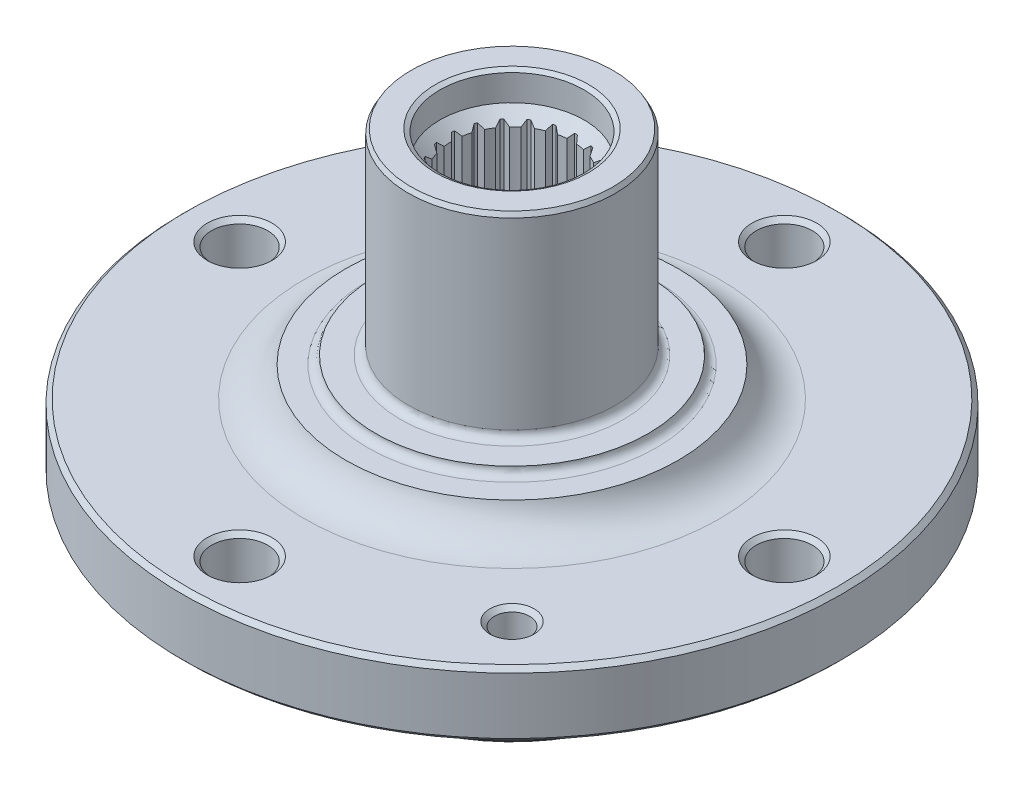
SolidWorks part; units mm, degrees
ref_plane "Front Plane" through (0, 0, 0) normal (0, 0, 1) x (1, 0, 0)
ref_plane "Top Plane" through (0, 0, 0) normal (0, 1, 0) x (1, 0, 0)
ref_plane "Right Plane" through (0, 0, 0) normal (1, 0, 0) x (0, 0, -1)
sketch "Sketch1" plane through (0, 0, 0) normal (0, 0, 1) x (1, 0, 0)
  line L0 (0, 72.238) -> (0, -80.5296) construction
  line L1 (13.25, 37.5) -> (13.25, 32.5)
  line L2 (13.25, 32.5) -> (11, 32.5)
  line L3 (11, 32.5) -> (11, -18.5)
  line L4 (11, -18.5) -> (25.5, -18.5)
  line L5 (25.5, -18.5) -> (25.5, -34.5)
  line L6 (25.5, -34.5) -> (28, -34.5)
  line L7 (28, -34.5) -> (28, -39.5)
  line L8 (30.25, -17.5) -> (30.25, -26)
  line L9 (30.25, -26) -> (30, -26)
  line L10 (30.25, -17.5) -> (60.5, -17.5)
  line L11 (60.5, -17.5) -> (60.5, -5.5)
  line L12 (60.5, -5.5) -> (30.5, -5.5)
  line L13 (30.5, -5.5) -> (30.5, 0)
  line L14 (30.5, 0) -> (25, 0)
  line L15 (25, 0) -> (25, 1.5)
  line L16 (25, 1.5) -> (19, 1.5)
  line L17 (19, 1.5) -> (19, 37.5)
  line L18 (13.25, 37.5) -> (19, 37.5)
  line L19 (30, -26) -> (30, -35)
  line L20 (30, -35) -> (29.5, -35)
  line L21 (29.5, -35) -> (29.5, -39.5)
  line L22 (29.5, -39.5) -> (28, -39.5)
  dimension "D1" = 11
  dimension "D2" = 5
  dimension "D3" = 19
  dimension "D4" = 25
  dimension "D5" = 30.5
  dimension "D6" = 60.5
  dimension "D7" = 25.5
  dimension "D8" = 28
  dimension "D9" = 30.25
  dimension "D10" = 30
  dimension "D11" = 29.5
  dimension "D12" = 5
  dimension "D13" = 21
  dimension "D14" = 12
  dimension "D15" = 13.25
  dimension "D16" = 36
  dimension "D17" = 1.5
  dimension "D18" = 5.5
  dimension "D19" = 5.5
  dimension "D20" = 8.5
  dimension "D21" = 17.5
  dimension "D22" = 22
revolve "Revolve1" add sketch "Sketch1" angle 360 about L0
sketch "Sketch2" plane through (0, -17.5, 0) normal (0, -1, 0) x (1, 0, 0)
  line L0 (0, 0) -> (-50, 0) construction
  circle A0 centre (0, 0) radius 50 construction
  circle A1 centre (-50, 0) radius 5.15
  circle A2 centre (35.3553, 35.3553) radius 3.25
  circle A3 centre (0, 50) radius 5.15
  circle A5 centre (50, 0) radius 5.15
  circle A6 centre (-35.3553, -35.3553) radius 3.25
  circle A7 centre (0, -50) radius 5.15
  circle A9 centre (-35.3553, 35.3553) radius 5.15 [skipped]
  circle A10 centre (35.3553, -35.3553) radius 5.15 [skipped]
  circle A11 centre (35.3553, 35.3553) radius 5.15 [skipped]
  circle A12 centre (-35.3553, -35.3553) radius 5.15 [skipped]
  point P21 (0, 0)
  dimension "D1" = 8
  dimension "D2" = 6.5
  dimension "D3" = 6.5
extrude "Cut-Extrude1" cut sketch "Sketch2" against normal blind 20
chamfer "Chamfer6" distance 1 angle 45 1 edges at (-11, -18.5, 0)
chamfer "Chamfer7" distance 2.5 angle 45 1 edges at (-11, 32.5, 0)
sketch "Sketch3" plane through (0, -18.5, 0) normal (0, -1, 0) x (1, 0, 0)
  line L0 (1.4996, 11.6545) -> (0.2154, 10.4911)
  line L1 (0, 0) -> (0, 11.75) construction
  line L2 (2.0013, 11.5789) -> (2.8855, 10.0886)
  line L3 (4.8683, 10.6946) -> (3.2983, 9.9615)
  line L4 (5.3254, 10.4745) -> (5.7311, 8.7899)
  line L5 (7.8045, 8.7845) -> (6.0881, 8.5467)
  line L6 (8.1764, 8.4394) -> (8.0675, 6.7101)
  line L7 (10.0472, 6.0938) -> (8.3369, 6.3724)
  line L8 (10.3008, 5.6544) -> (9.687, 4.034)
  line L9 (11.3971, 2.8616) -> (9.845, 3.6319)
  line L10 (11.51, 2.367) -> (10.4458, 0.9994)
  line L11 (11.7344, -0.625) -> (10.4782, 0.5687)
  line L12 (11.6964, -1.1309) -> (10.2765, -2.124)
  line L13 (11.029, -4.056) -> (10.1805, -2.5451)
  line L14 (10.8436, -4.5282) -> (9.194, -5.0587)
  line L15 (9.3436, -7.1267) -> (8.9781, -5.4328)
  line L16 (9.0273, -7.5233) -> (7.2946, -7.5439)
  line L17 (6.828, -9.5642) -> (6.978, -7.8379)
  line L18 (6.4088, -9.8499) -> (4.747, -9.3589)
  line L19 (3.7057, -11.1519) -> (4.3579, -9.5465)
  line L20 (3.2209, -11.3014) -> (1.7777, -10.3424)
  line L21 (0.2541, -11.7487) -> (1.3505, -10.4069)
  line L22 (-0.2532, -11.7487) -> (-1.3497, -10.4069)
  line L23 (-3.2201, -11.3017) -> (-1.7768, -10.3427)
  line L24 (-3.7048, -11.1522) -> (-4.3571, -9.5468)
  line L25 (-6.4081, -9.8505) -> (-4.7463, -9.3595)
  line L26 (-6.8273, -9.5647) -> (-6.9773, -7.8384)
  line L27 (-9.0268, -7.5241) -> (-7.2941, -7.5447)
  line L28 (-9.3431, -7.1275) -> (-8.9776, -5.4336)
  line L29 (-10.8434, -4.5292) -> (-9.1937, -5.0596)
  line L30 (-11.0287, -4.0569) -> (-10.1802, -2.5461)
  line L31 (-11.6965, -1.1319) -> (-10.2765, -2.125)
  line L32 (-11.7344, -0.6259) -> (-10.4783, 0.5677)
  line L33 (-11.5103, 2.366) -> (-10.4462, 0.9985)
  line L34 (-11.3974, 2.8606) -> (-9.8453, 3.631)
  line L35 (-10.3014, 5.6536) -> (-9.6876, 4.0331)
  line L36 (-10.0478, 6.0929) -> (-8.3375, 6.3716)
  line L37 (-8.1772, 8.4388) -> (-8.0683, 6.7094)
  line L38 (-7.8053, 8.7838) -> (-6.0889, 8.546)
  line L39 (-5.3264, 10.4741) -> (-5.7321, 8.7894)
  line L40 (-4.8693, 10.6942) -> (-3.2993, 9.961)
  line L41 (-2.0024, 11.5787) -> (-2.8866, 10.0885)
  line L42 (-1.5007, 11.6543) -> (-0.2165, 10.4909)
  arc A0 (3.2983, 9.9615) -> (5.7311, 8.7899) centre (0.0002, 0.0012) cw
  arc A1 (0.2154, 10.4911) -> (2.8855, 10.0886) centre (-0.0003, 0.0011) cw
  arc A2 (4.8683, 10.6946) -> (5.3254, 10.4745) centre (0, 0.0007) cw
  arc A3 (6.0881, 8.5467) -> (8.0675, 6.7101) centre (0.0006, 0.001) cw
  arc A4 (7.8045, 8.7845) -> (8.1764, 8.4394) centre (0.0003, 0.0007) cw
  arc A5 (8.3369, 6.3724) -> (9.687, 4.034) centre (0.001, 0.0007) cw
  arc A6 (10.0472, 6.0938) -> (10.3008, 5.6544) centre (0.0006, 0.0005) cw
  arc A7 (9.845, 3.6319) -> (10.4458, 0.9994) centre (0.0013, 0.0004) cw
  arc A8 (11.3971, 2.8616) -> (11.51, 2.367) centre (0.0009, 0.0003) cw
  arc A9 (10.4782, 0.5687) -> (10.2765, -2.124) centre (0.0015, -0.0001) cw
  arc A10 (11.7344, -0.625) -> (11.6964, -1.1309) centre (0.0011, 0) cw
  arc A11 (10.1805, -2.5451) -> (9.194, -5.0587) centre (0.0016, -0.0006) cw
  arc A12 (11.029, -4.056) -> (10.8436, -4.5282) centre (0.0011, -0.0004) cw
  arc A13 (8.9781, -5.4328) -> (7.2946, -7.5439) centre (0.0015, -0.001) cw
  arc A14 (9.3436, -7.1267) -> (9.0273, -7.5233) centre (0.0011, -0.0007) cw
  arc A15 (6.978, -7.8379) -> (4.747, -9.3589) centre (0.0012, -0.0015) cw
  arc A16 (6.828, -9.5642) -> (6.4088, -9.8499) centre (0.001, -0.0011) cw
  arc A17 (4.3579, -9.5465) -> (1.7777, -10.3424) centre (0.0009, -0.0018) cw
  arc A18 (3.7057, -11.1519) -> (3.2209, -11.3014) centre (0.0007, -0.0013) cw
  arc A19 (1.3505, -10.4069) -> (-1.3497, -10.4069) centre (0.0004, -0.002) cw
  arc A20 (0.2541, -11.7487) -> (-0.2532, -11.7487) centre (0.0004, -0.0015) cw
  arc A21 (-1.7768, -10.3427) -> (-4.3571, -9.5468) centre (0, -0.0021) cw
  arc A22 (-3.2201, -11.3017) -> (-3.7048, -11.1522) centre (0.0001, -0.0016) cw
  arc A23 (1.4996, 11.6545) -> (2.0013, 11.5789) centre (-0.0004, 0.0007) cw
  arc A25 (-4.7463, -9.3595) -> (-6.9773, -7.8384) centre (-0.0005, -0.002) cw
  arc A26 (-6.4081, -9.8505) -> (-6.8273, -9.5647) centre (-0.0003, -0.0016) cw
  arc A27 (-7.2941, -7.5447) -> (-8.9776, -5.4336) centre (-0.001, -0.0018) cw
  arc A28 (-9.0268, -7.5241) -> (-9.3431, -7.1275) centre (-0.0006, -0.0015) cw
  arc A29 (-9.1937, -5.0596) -> (-10.1802, -2.5461) centre (-0.0013, -0.0015) cw
  arc A30 (-10.8434, -4.5292) -> (-11.0287, -4.0569) centre (-0.0009, -0.0013) cw
  arc A31 (-10.2765, -2.125) -> (-10.4783, 0.5677) centre (-0.0016, -0.0011) cw
  arc A32 (-11.6965, -1.1319) -> (-11.7344, -0.6259) centre (-0.0011, -0.001) cw
  arc A33 (-10.4462, 0.9985) -> (-9.8453, 3.631) centre (-0.0017, -0.0006) cw
  arc A34 (-11.5103, 2.366) -> (-11.3974, 2.8606) centre (-0.0012, -0.0007) cw
  arc A35 (-9.6876, 4.0331) -> (-8.3375, 6.3716) centre (-0.0016, -0.0001) cw
  arc A36 (-10.3014, 5.6536) -> (-10.0478, 6.0929) centre (-0.0012, -0.0003) cw
  arc A37 (-8.0683, 6.7094) -> (-6.0889, 8.546) centre (-0.0015, 0.0003) cw
  arc A38 (-8.1772, 8.4388) -> (-7.8053, 8.7838) centre (-0.0012, 0) cw
  arc A39 (-5.7321, 8.7894) -> (-3.2993, 9.961) centre (-0.0012, 0.0007) cw
  arc A40 (-5.3264, 10.4741) -> (-4.8693, 10.6942) centre (-0.001, 0.0003) cw
  arc A41 (-2.8866, 10.0885) -> (-0.2165, 10.4909) centre (-0.0008, 0.001) cw
  arc A42 (-2.0024, 11.5787) -> (-1.5007, 11.6543) centre (-0.0007, 0.0005) cw
  point P142 (-0.0001, -0.0005)
  dimension "D1" = 21
extrude "Cut-Extrude4" cut sketch "Sketch3" against normal blind 100
chamfer "Chamfer1" distance 0.8 angle 45 11 edges at (55.15, -17.5, 0) (55.15, -5.5, 0) (5.15, -17.5, -50) (5.15, -5.5, -50) (-32.1053, -17.5, -35.3553) (-32.1053, -5.5, -35.3553) (-44.85, -17.5, 0) (-44.85, -5.5, 0) (38.6053, -5.5, 35.3553) (5.15, -17.5, 50) (5.15, -5.5, 50)
chamfer "Chamfer2" distance 0.8 angle 45 2 edges at (-60.5, -17.5, 0) (-60.5, -5.5, 0)
fillet "Fillet1" radius 2 1 edges at (-30.25, -17.5, 0)
fillet "Fillet2" radius 1.5 2 edges at (-25.5, -18.5, 0) (-28, -34.5, 0)
chamfer "Chamfer3" distance 0.5 angle 45 2 edges at (-29.5, -39.5, 0) (-28, -39.5, 0)
fillet "Fillet3" radius 8 1 edges at (-30.5, -5.5, 0)
fillet "Fillet4" radius 1.5 1 edges at (-25, 0, 0)
fillet "Fillet5" radius 1.5 1 edges at (-19, 1.5, 0)
chamfer "Chamfer5" distance 0.8 angle 30 2 edges at (-13.25, 37.5, 0) (-19, 37.5, 0) first distance on face at (-13.25, 37.5, 0) first distance on face at (19, 3, 0)
